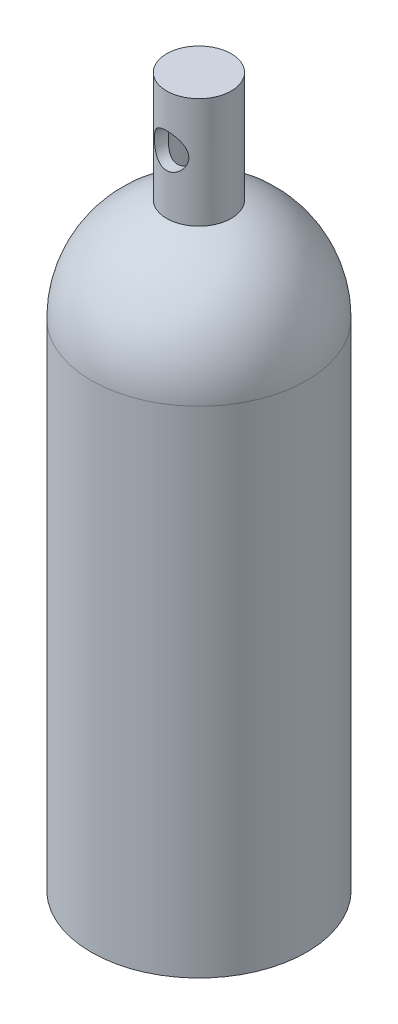
SolidWorks part; units mm, degrees
ref_plane "Front Plane" through (0, 0, 0) normal (0, 0, 1) x (1, 0, 0)
ref_plane "Top Plane" through (0, 0, 0) normal (0, 1, 0) x (1, 0, 0)
ref_plane "Right Plane" through (0, 0, 0) normal (1, 0, 0) x (0, 0, -1)
sketch "Sketch_Toothpaste Tank" plane through (0, 0, 0) normal (0, 1, 0) x (1, 0, 0)
  circle A0 centre (0, 0) radius 50
  dimension "D1" = 100
extrude "Toothpaste Tank" add sketch "Sketch_Toothpaste Tank" against normal blind 230
shell "Shell_Tank Space" thickness 5 removed face at (0, 0, 50)
sketch "Sketch_Tank Top" plane through (0, 0, 0) normal (1, 0, 0) x (0, 0, -1)
  line L0 (0, 0) -> (0, 45) construction
  line L1 (0, 48.9898) -> (0, 50) construction
  line L2 (0, 0) -> (-45, 0) construction
  line L3 (-10, 48.9898) -> (0, 48.9898) construction
  line L4 (0, 45) -> (0, 48.9898) construction
  line L5 (-45, 0) -> (-50, 0)
  line L8 (-10, 48.9898) -> (-10, 43.8748)
  line L9 (-10, 48.9898) -> (-10, 93.8748)
  line L10 (-10, 98.9898) -> (-15, 98.9898)
  line L11 (-15, 98.9898) -> (-15, 47.697)
  line L12 (-10, 98.9898) -> (0, 98.9898)
  line L13 (0, 98.9898) -> (0, 93.8748)
  line L14 (0, 93.8748) -> (-10, 93.8748)
  line L15 (-10, 93.8748) -> (-10, 98.9898) construction
  arc A0 (-50, 0) -> (-15, 47.697) centre (0, 0) cw
  arc A1 (-10, 48.9898) -> (0, 50) centre (0, 0) cw construction
  arc A2 (-45, 0) -> (-10, 43.8748) centre (0, 0) cw
  arc A3 (-10, 43.8748) -> (0, 45) centre (0, 0) cw construction
  arc A4 (-15, 47.697) -> (-10, 48.9898) centre (0, 0) cw construction
  point P3 (0, 92.1328)
  point P18 (-10, 92.7652)
  point P20 (0, 0)
  dimension "D1" = 10
  dimension "D2" = 50
  dimension "D3" = 5
revolve "Revolve_Tank Top" add sketch "Sketch_Tank Top" angle 360 about L1
sketch "Sketch_Valve" plane through (0, 0, 0) normal (0, 0, 1) x (1, 0, 0)
  line L1 (0, 0) -> (0, 75) construction
  circle A1 centre (0, 75) radius 8
  dimension "D2" = 16
  dimension "D1" = 75
extrude "Cut_Valve" cut sketch "Sketch_Valve" along normal up to next
